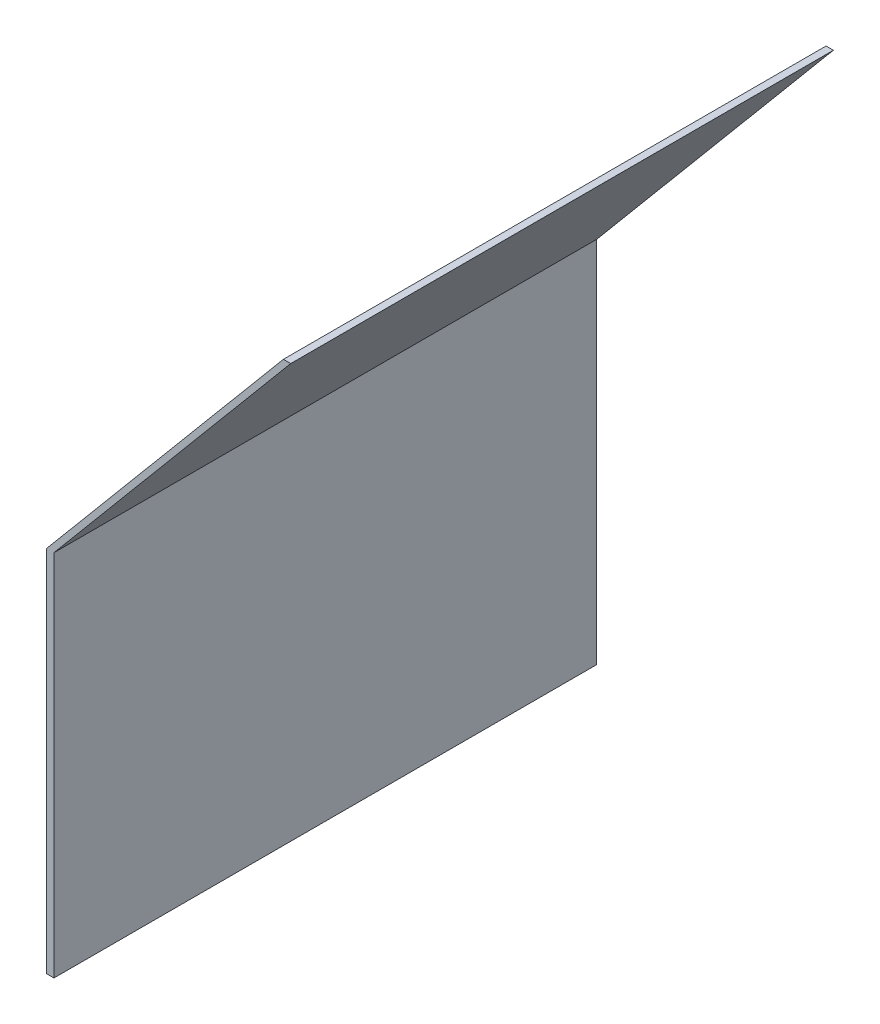
SolidWorks part; units mm, degrees
ref_plane "Front Plane" through (0, 0, 0) normal (0, 0, 1) x (1, 0, 0)
ref_plane "Top Plane" through (0, 0, 0) normal (0, 1, 0) x (1, 0, 0)
ref_plane "Right Plane" through (0, 0, 0) normal (1, 0, 0) x (0, 0, -1)
sketch "Sketch1" plane through (0, 0, 0) normal (0, 0, 1) x (1, 0, 0)
  line L0 (0, 0) -> (1.5189, 0)
  line L1 (1.5189, 0) -> (1.5189, 76.2)
  line L2 (1.5189, 76.2) -> (50.4993, 134.5726)
  line L3 (50.4993, 134.5726) -> (48.9804, 134.5726)
  line L4 (48.9804, 134.5726) -> (0, 76.2)
  line L5 (0, 76.2) -> (0, 0)
  point P3 (0, 0)
  dimension "D1" = 1.5189
  dimension "D2" = 1.5189
  dimension "D3" = 76.2
  dimension "D4" = 76.2
  dimension "D5" = 140
extrude "Boss-Extrude1" add sketch "Sketch1" along normal blind 112.268
